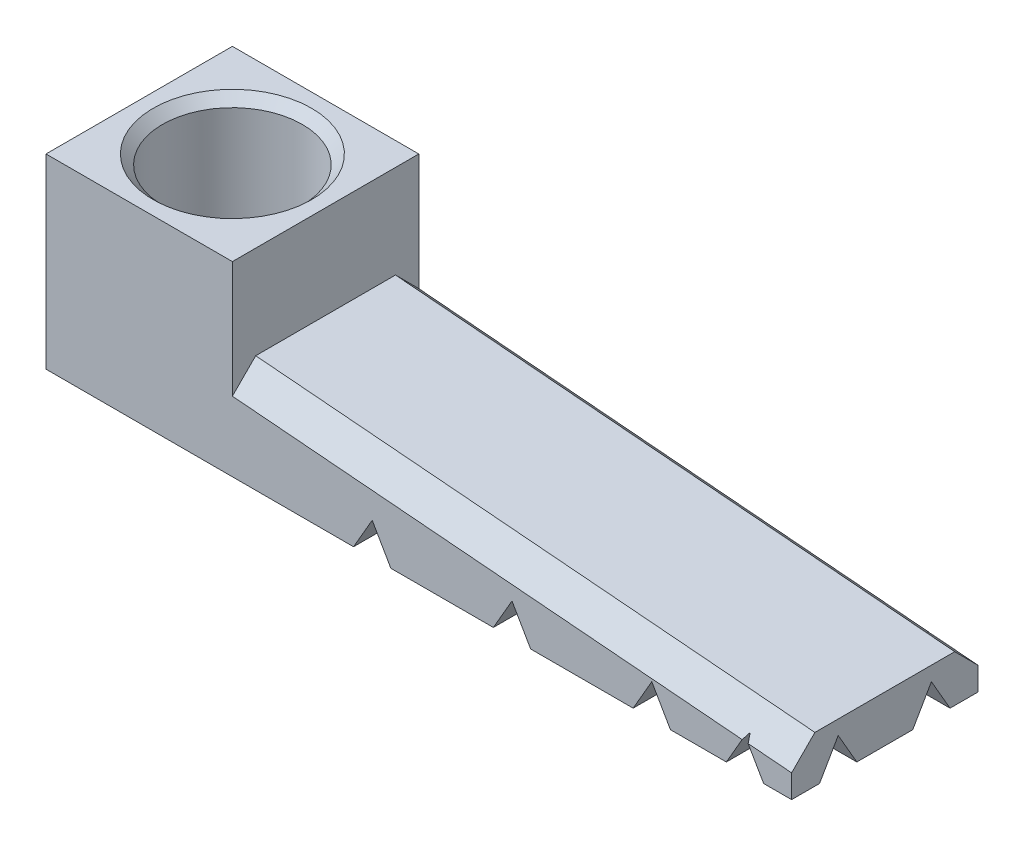
SolidWorks part; units mm, degrees
ref_plane "Front Plane" through (0, 0, 0) normal (0, 0, 1) x (1, 0, 0)
ref_plane "Top Plane" through (0, 0, 0) normal (0, 1, 0) x (1, 0, 0)
ref_plane "Right Plane" through (0, 0, 0) normal (1, 0, 0) x (0, 0, -1)
sketch "Sketch1" plane through (0, 0, 0) normal (0, 0, 1) x (1, 0, 0)
  line L0 (0, 0) -> (0, 20)
  line L1 (0, 20) -> (20, 20)
  line L2 (20, 20) -> (20, 10)
  line L3 (0, 0) -> (80, 0)
  line L4 (80, 0) -> (80, 5)
  line L5 (80, 5) -> (20, 10)
  dimension "D1" = 20
  dimension "D2" = 20
  dimension "D3" = 10
  dimension "D4" = 80
  dimension "D5" = 5
extrude "Boss-Extrude1" add sketch "Sketch1" along normal blind 20
chamfer "Chamfer1" distance 2.5 angle 45 2 edges at (50, 7.5, 0) (50, 7.5, 20)
ref_plane "Plane1" through (0, 0, 0) normal (0, -1, 0) x (-1, 0, 0)
sketch "Sketch2" plane through (0, 0, 0) normal (0, -1, 0) x (-1, 0, 0)
  line L0 (0, -10) -> (-20, -10) construction
  line L1 (0, -20) -> (0, 0) construction
  line L2 (-10, -1010) -> (-10, 48990) construction
  circle A0 centre (-10, -10) radius 7.5
  point P7 (-10, -10)
  dimension "D1" = 15
extrude "Cut-Extrude1" cut sketch "Sketch2" against normal through all
ref_plane "Plane2" through (80, 0, 0) normal (1, 0, 0) x (0, 0, -1)
sketch "Sketch3" plane through (80, 0, 0) normal (1, 0, 0) x (0, 0, -1)
  line L0 (-15, -997.6224) -> (-15, 49002.3776) construction
  line L2 (-5, -998.5989) -> (-5, 49001.4011) construction
  line L3 (0, 0) -> (0, 2.4913) construction
  line L4 (-20, 20) -> (-20, 0) construction
  line L5 (-20, 0) -> (0, 0) construction
  line L6 (-15, 3.4641) -> (-17, 0)
  line L7 (-17, 0) -> (-13, 0)
  line L8 (-13, 0) -> (-15, 3.4641)
  line L9 (-10, -995) -> (-10, 49005) construction
  line L10 (-20, 0) -> (-20, 2.4913) construction
  line L11 (-7, 0) -> (-5, 3.4641)
  line L12 (-3, 0) -> (-7, 0)
  line L13 (-5, 3.4641) -> (-3, 0)
  circle A0 centre (-15, 1.1547) radius 1.1547 construction
  circle A1 centre (-5, 1.1547) radius 1.1547 construction
  dimension "D3" = 4
  dimension "D1" = 5
  dimension "D2" = 5
  dimension "D4" = 10
extrude "Cut-Extrude2" cut sketch "Sketch3" against normal up to surface (60 mm away) up to face at (20, 12.4971, 10)
sketch "Sketch4" plane through (0, 0, 0) normal (0, 0, 1) x (1, 0, 0)
  line L0 (0, 0) -> (80, 0) construction
  line L1 (75, 3.4641) -> (73, 0)
  line L2 (73, 0) -> (77, 0)
  line L3 (77, 0) -> (75, 3.4641)
  line L4 (80, 0) -> (80, 2.4913) construction
  line L6 (65, 3.4641) -> (63, 0)
  line L7 (63, 0) -> (67, 0)
  line L8 (67, 0) -> (65, 3.4641)
  line L9 (50, 3.4641) -> (48, 0)
  line L10 (48, 0) -> (52, 0)
  line L11 (52, 0) -> (50, 3.4641)
  line L12 (35, 3.4641) -> (33, 0)
  line L13 (33, 0) -> (37, 0)
  line L14 (37, 0) -> (35, 3.4641)
  circle A0 centre (75, 1.1547) radius 1.1547 construction
  circle A1 centre (65, 1.1547) radius 1.1547 construction
  circle A2 centre (50, 1.1547) radius 1.1547 construction
  circle A3 centre (35, 1.1547) radius 1.1547 construction
  dimension "D1" = 4
  dimension "D2" = 5
  dimension "D3" = 4
  dimension "D4" = 15
  dimension "D5" = 4
  dimension "D6" = 4
  dimension "D7" = 30
  dimension "D8" = 45
extrude "Cut-Extrude3" cut sketch "Sketch4" along normal through all
chamfer "Chamfer2" distance 1 angle 45 2 edges at (10, 0, 2.5) (10, 20, 2.5)
